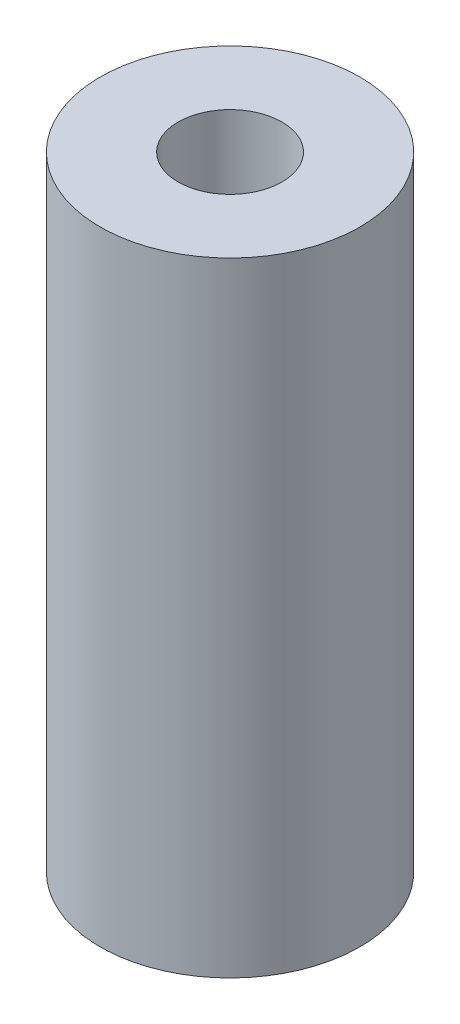
SolidWorks part; units mm, degrees
material "Nylon 101"
ref_plane "Front Plane" through (0, 0, 0) normal (0, 0, 1) x (1, 0, 0)
ref_plane "Top Plane" through (0, 0, 0) normal (0, 1, 0) x (1, 0, 0)
ref_plane "Right Plane" through (0, 0, 0) normal (1, 0, 0) x (0, 0, -1)
sketch "Sketch1" plane through (0, 0, 0) normal (0, 1, 0) x (1, 0, 0)
  circle A0 centre (0, 0) radius 2.54
  circle A1 centre (0, 0) radius 6.35
  dimension "D1" = 5.08
  dimension "D2" = 12.7
extrude "Boss-Extrude1" add sketch "Sketch1" along normal blind 30.48
